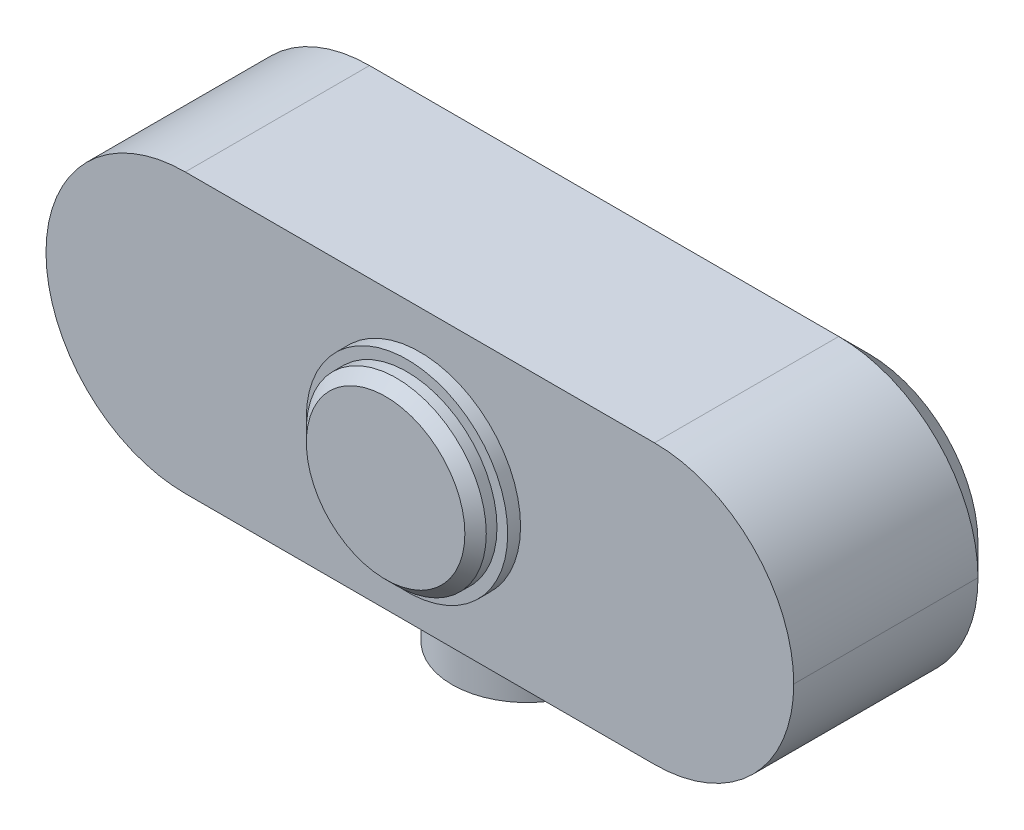
SolidWorks part; units mm, degrees
ref_plane "Front Plane" through (0, 0, 0) normal (0, 0, 1) x (1, 0, 0)
ref_plane "Top Plane" through (0, 0, 0) normal (0, 1, 0) x (1, 0, 0)
ref_plane "Right Plane" through (0, 0, 0) normal (1, 0, 0) x (0, 0, -1)
sketch "Sketch1" plane through (0, 0, 0) normal (0, 0, 1) x (1, 0, 0)
  line L1 (34.9, -13) -> (-34.9, -13)
  line L2 (34.9, -13) -> (34.9, 13)
  line L3 (34.9, 13) -> (-34.9, 13)
  line L4 (-34.9, -13) -> (-34.9, 13)
  line L5 (34.9, -13) -> (-34.9, 13) construction
  line L6 (34.9, 13) -> (-34.9, -13) construction
  point P0 (0, 0)
  dimension "D1" = 69.8
  dimension "26" = 26
extrude "Boss-Extrude1" add sketch "Sketch1" along normal blind 20
fillet "Fillet1" radius 13 4 edges at (-34.9, -13, 10) (-34.9, 13, 10) (34.9, -13, 10) (34.9, 13, 10)
sketch "Sketch2" plane through (0, 0, 20) normal (0, 0, 1) x (1, 0, 0)
  circle A0 centre (0, 0) radius 9.4
  dimension "D1" = 18.8
extrude "Boss-Extrude2" add sketch "Sketch2" along normal blind 1.2
sketch "Sketch3" plane through (0, 0, 21.2) normal (0, 0, 1) x (1, 0, 0)
  circle A0 centre (0, 0) radius 8.4
  dimension "D1" = 16.8
extrude "Boss-Extrude3" add sketch "Sketch3" along normal blind 2
chamfer "Chamfer1" distance 1 angle 45 1 edges at (8.4, 0, 23.2)
sketch "Sketch4" plane through (0, -13, 0) normal (0, -1, 0) x (1, 0, 0)
  line L0 (0, 0) -> (0, 20) construction
  line L1 (-21.9, 20) -> (21.9, 20) construction
  circle A0 centre (0, 10) radius 7
  circle A1 centre (0, 10) radius 5
  dimension "D1" = 14
  dimension "D2" = 10
extrude "Boss-Extrude4" add sketch "Sketch4" along normal blind 6
sketch "Sketch5" plane through (0, 0, 0) normal (0, 0, -1) x (-1, 0, 0)
  line L0 (-32.147, -8) -> (32.147, -8) construction
  line L1 (21.9, -13) -> (-21.9, -13) construction
  line L2 (-18.9, 13) -> (-18.9, -13) construction
  line L3 (-21.9, 13) -> (21.9, 13) construction
  arc A0 (-34.9, 0) -> (-21.9, -13) centre (-21.9, 0) ccw construction
  arc A1 (21.9, -13) -> (34.9, 0) centre (21.9, 0) ccw construction
  circle A2 centre (-18.9, -8) radius 1.75
  point P17 (-18.9, -8)
  point P18 (-16.0654, -8)
  dimension "D3" = 3.5
  dimension "D1" = 5
  dimension "D2" = 16
extrude "Boss-Extrude5" add sketch "Sketch5" along normal blind 5
chamfer "Chamfer2" distance 2.8 angle 45 6 edges at (-31.0924, -9.1924, 0) (-31.0924, 9.1924, 0) (0, -13, 0) (0, 13, 0) (31.0924, -9.1924, 0) (31.0924, 9.1924, 0)
sketch "Sketch6" plane through (0, 0, 0) normal (0, 0, -1) x (-1, 0, 0)
  line L0 (-21.4, -10.2) -> (-21.4, -8)
  line L1 (-21.9, -10.2) -> (21.9, -10.2) construction
  line L2 (-18.9, -8) -> (-18.9, -10.2) construction
  line L3 (-16.4, -8) -> (-16.4, -10.2)
  line L4 (-21.4, -10.2) -> (-16.4, -10.2)
  arc A0 (-21.4, -8) -> (-16.4, -8) centre (-18.9, -8) cw
  circle A2 centre (-18.9, -8) radius 1.75
  circle A3 centre (-18.9, -8) radius 1.75 construction
  dimension "D2" = 2.5
  dimension "D1" = 5
extrude "Cut-Extrude1" cut sketch "Sketch6" against normal blind 1
